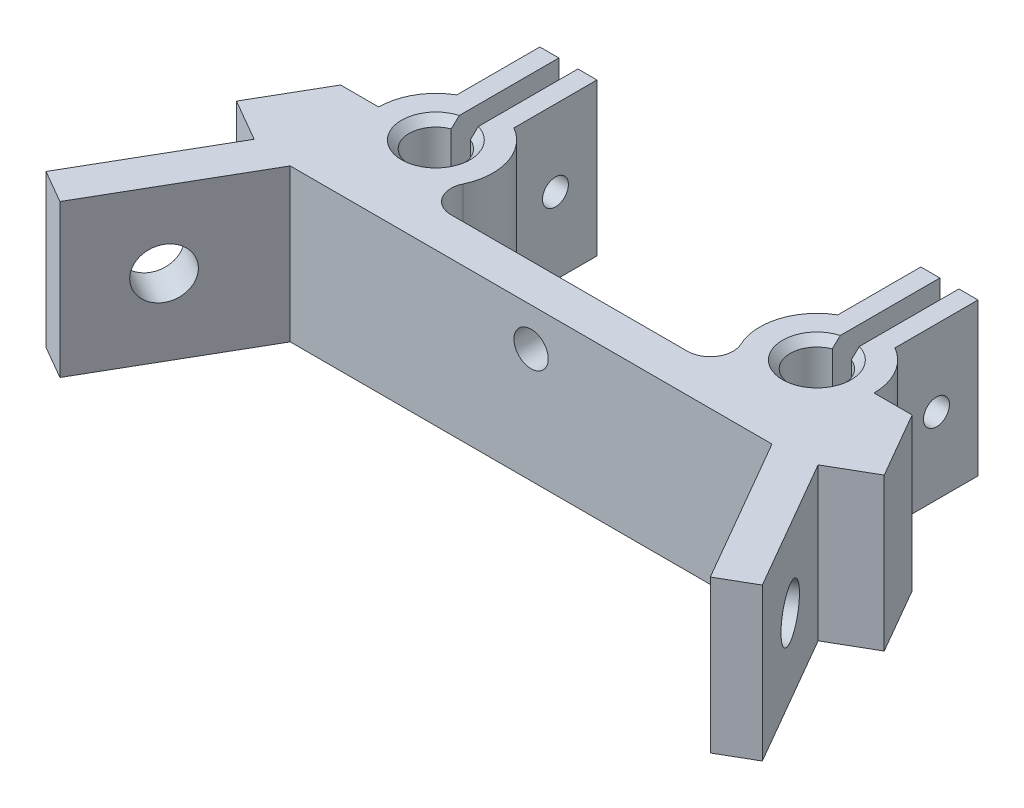
SolidWorks part; units mm, degrees
ref_plane "Front Plane" through (0, 0, 0) normal (0, 0, 1) x (1, 0, 0)
ref_plane "Top Plane" through (0, 0, 0) normal (0, 1, 0) x (1, 0, 0)
ref_plane "Right Plane" through (0, 0, 0) normal (1, 0, 0) x (0, 0, -1)
sketch "Sketch1" plane through (0, 0, 0) normal (0, 1, 0) x (1, 0, 0)
  line L0 (0, 116.7614) -> (0, -100.8523) construction
  line L1 (23.75, 120.7692) -> (23.75, 134.8951)
  line L2 (28.75, 134.8951) -> (28.75, 123.9952)
  line L3 (25, -2.1466) -> (25, 14.9187) construction
  line L4 (23.75, 134.8951) -> (21.25, 134.8951)
  line L5 (21.25, 134.8951) -> (21.25, 123.9952)
  line L6 (26.25, 134.8951) -> (28.75, 134.8951)
  line L7 (26.25, 120.7692) -> (26.25, 134.8951)
  line L8 (-25, -0.2491) -> (-25, 16.8161) construction
  line L9 (-26.25, 120.7692) -> (-26.25, 134.8951)
  line L10 (-26.25, 134.8951) -> (-28.75, 134.8951)
  line L11 (-21.25, 134.8951) -> (-21.25, 123.9952)
  line L12 (-23.75, 134.8951) -> (-21.25, 134.8951)
  line L13 (-28.75, 134.8951) -> (-28.75, 123.9952)
  line L14 (-23.75, 120.7692) -> (-23.75, 134.8951)
  line L15 (-15.5132, 110) -> (15.5132, 110)
  line L16 (-31.611, 105) -> (31.611, 105)
  line L17 (-32.5, 117.5) -> (-37.5, 117.5)
  line L18 (0, 110) -> (-95.2628, -55) construction
  line L19 (-95.2628, -55) -> (95.2628, -55) construction
  line L20 (95.2628, -55) -> (0, 110) construction
  line L21 (-37.5, 117.5) -> (-42.5, 108.8397)
  line L22 (-47.0007, 88.3442) -> (-42.6706, 85.8442)
  line L23 (-42.6706, 85.8442) -> (-31.611, 105)
  line L24 (42.6706, 85.8442) -> (31.611, 105)
  line L25 (47.0007, 88.3442) -> (42.6706, 85.8442)
  line L26 (47.0007, 88.3442) -> (37.0007, 105.6647)
  line L27 (32.5, 117.5) -> (37.5, 117.5)
  line L28 (-47.0007, 88.3442) -> (-37.0007, 105.6647)
  line L29 (-37.0007, 105.6647) -> (-42.5, 108.8397)
  line L30 (37.0007, 105.6647) -> (42.5, 108.8397)
  line L31 (37.5, 117.5) -> (42.5, 108.8397)
  arc A0 (21.25, 123.9952) -> (18.2237, 114.2857) centre (25, 117.5) ccw
  arc A1 (23.75, 120.7692) -> (26.25, 120.7692) centre (25, 117.5) ccw
  arc A2 (-23.75, 120.7692) -> (-26.25, 120.7692) centre (-25, 117.5) cw
  arc A3 (-21.25, 123.9952) -> (-18.2237, 114.2857) centre (-25, 117.5) cw
  circle A4 centre (0, 0) radius 110 construction
  circle A5 centre (0, 0) radius 55 construction
  arc A6 (15.5132, 110) -> (18.2237, 114.2857) centre (15.5132, 113) ccw
  arc A7 (-18.2237, 114.2857) -> (-15.5132, 110) centre (-15.5132, 113) ccw
  arc A8 (-28.75, 123.9952) -> (-32.5, 117.5) centre (-25, 117.5) ccw
  arc A9 (28.75, 123.9952) -> (32.5, 117.5) centre (25, 117.5) cw
  point P12 (23.75, 124.8951)
  point P13 (26.25, 124.8951)
  point P27 (-26.25, 124.8951)
  point P28 (-23.75, 124.8951)
  point P67 (0, 0)
  dimension "D2" = 7
  dimension "D3" = 4
  dimension "D5" = 2.5
  dimension "D10" = 120
  dimension "D11" = 10
  dimension "D7" = 220
  dimension "D13" = 3
  dimension "D14" = 7.5
  dimension "D1" = 50
  dimension "D4" = 10
  dimension "D6" = 2.5
  dimension "D8" = 5
  dimension "D9" = 5
  dimension "D12" = 5
  dimension "D15" = 20
  dimension "D16" = 6.35
extrude "Boss-Extrude1" add sketch "Sketch1" along normal blind 20 contours A3 L11 L12 L14 A2 L9 L10 L13 | A1 L1 L4 L5 A0 L2 L6 L7 | L15 A3 L16 A0 region at (25, 0, -112.9397)
sketch "Sketch2" plane through (0, 0, 0) normal (1, 0, 0) x (0, 0, -1)
  line L0 (123.9952, 20) -> (123.9952, 0) construction
  line L3 (134.8951, 10) -> (123.9952, 10) construction
  line L4 (134.8951, 20) -> (134.8951, 0) construction
  circle A0 centre (129.4451, 10) radius 1.7
  dimension "D1" = 3.4
extrude "Cut-Extrude1" cut sketch "Sketch2" against normal mid plane 57.5
sketch "Sketch4" plane through (0, 0, -105) normal (0, 0, 1) x (1, 0, 0)
  line L0 (-31.611, 20) -> (31.611, 20) construction
  circle A0 centre (0, 15) radius 2.25
  point P2 (0, 20)
  dimension "D2" = 5
  dimension "D1" = 4.5
extrude "Cut-Extrude2" cut sketch "Sketch4" against normal up to next contours A0 region at (0, 15, -105)
chamfer "Chamfer1" distance 1 angle 45 2 edges at (25, 20, -114) (-25, 20, -114)
sketch "Sketch5" plane through (-73.5047, 0, -42.438) normal (-0.866, 0, -0.5) x (-0.5, 0, 0.866)
  line L0 (-53.008, 10) -> (-73.008, 10) construction
  line L1 (-53.008, 20) -> (-53.008, 0) construction
  line L2 (-73.008, 20) -> (-73.008, 0) construction
  circle A1 centre (-63.008, 10) radius 3.3
  dimension "D1" = 6.6
extrude "Cut-Extrude3" cut sketch "Sketch5" against normal up to next
mirror "Mirror1" about plane through (0, 0, 0) normal (1, 0, 0) of "Cut-Extrude3"
equation "\"RodSpacing\"= 50"
equation "\"D1@Sketch1\"=\"RodSpacing\""
equation "\"Clamp_Gap\"=2.5"
equation "\"D5@Sketch1\"=\"Clamp_Gap\""
equation "\"D6@Sketch1\"=\"Clamp_Gap\""
equation "\"D1@Cut-Extrude1\"=\"RodSpacing\"+(3*\"Clamp_Gap\")"
